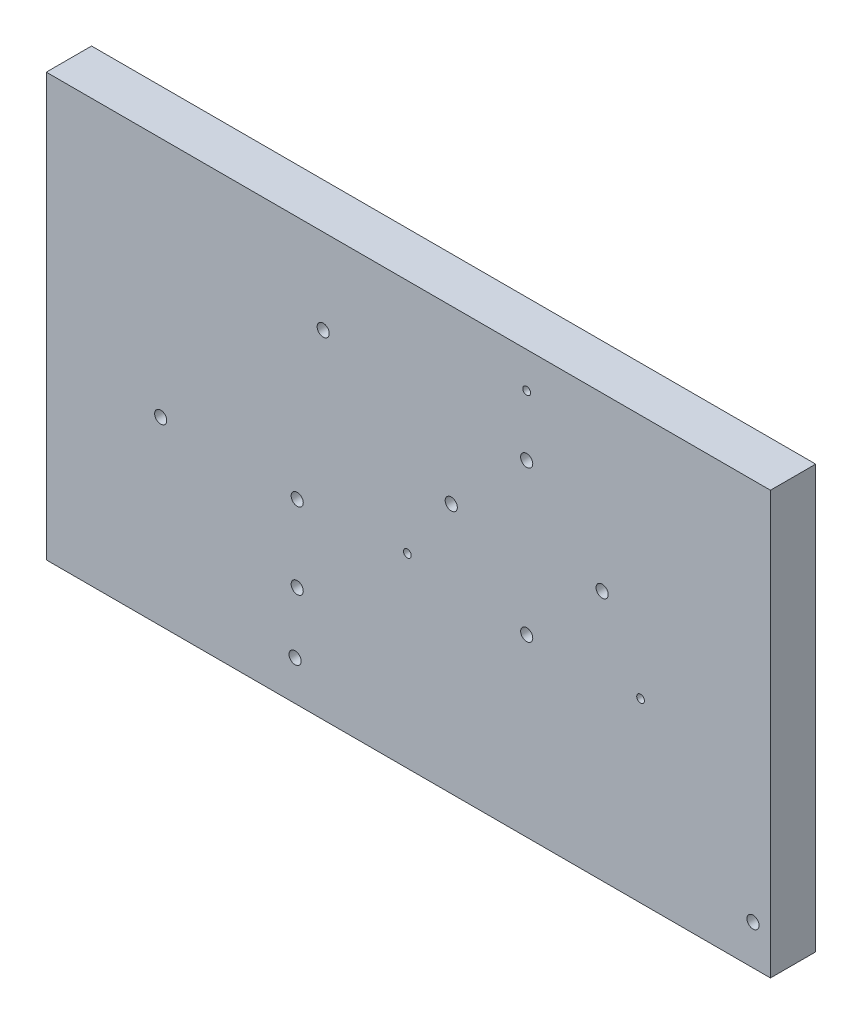
SolidWorks part; units mm, degrees
ref_plane "Front Plane" through (0, 0, 0) normal (0, 0, 1) x (1, 0, 0)
ref_plane "Top Plane" through (0, 0, 0) normal (0, 1, 0) x (1, 0, 0)
ref_plane "Right Plane" through (0, 0, 0) normal (1, 0, 0) x (0, 0, -1)
sketch "Sketch1" plane through (0, 0, 0) normal (0, 0, 1) x (1, 0, 0)
  line L1 (-152.4, -88.9) -> (152.4, -88.9)
  line L2 (-152.4, -88.9) -> (-152.4, 88.9)
  line L3 (-152.4, 88.9) -> (152.4, 88.9)
  line L4 (152.4, -88.9) -> (152.4, 88.9)
  line L5 (-152.4, -88.9) -> (152.4, 88.9) construction
  line L6 (-152.4, 88.9) -> (152.4, -88.9) construction
  point P0 (0, 0)
  dimension "D1" = 304.8
  dimension "D2" = 177.8
extrude "Boss-Extrude1" add sketch "Sketch1" against normal blind 19.05
sketch "Sketch2" plane through (0, 0, 0) normal (0, 0, 1) x (1, 0, 0)
  circle A1 centre (-104.2487, -12.7585) radius 2.5527
  circle A2 centre (-104.2487, -12.7585) radius 2.5527
  circle A3 centre (-46.7932, -46.1745) radius 2.5527
  circle A4 centre (-46.7932, -46.1745) radius 2.5527
  circle A5 centre (18.0555, 16.7132) radius 2.5527
  circle A6 centre (18.0555, 16.7132) radius 2.5527
  circle A7 centre (-35.8518, 53.1355) radius 2.5527
  circle A8 centre (-35.8518, 53.1355) radius 2.5527
  circle A9 centre (-47.6939, -72.1868) radius 2.5527
  circle A10 centre (-47.6939, -72.1868) radius 2.5527
  circle A11 centre (49.8055, 48.4632) radius 2.5527
  circle A12 centre (49.8055, 48.4632) radius 2.5527
  circle A13 centre (81.5555, 16.7132) radius 2.5527
  circle A14 centre (81.5555, 16.7132) radius 2.5527
  circle A15 centre (49.8055, -15.0368) radius 2.5527
  circle A16 centre (49.8055, -15.0368) radius 2.5527
  circle A17 centre (-46.7932, -14.0022) radius 2.5527
  circle A18 centre (-46.7932, -14.0022) radius 2.5527
  circle A19 centre (49.8055, 73.8632) radius 1.6319
  circle A20 centre (49.8055, 73.8632) radius 1.6319
  circle A21 centre (145.0555, -72.1868) radius 2.5527
  circle A22 centre (145.0555, -72.1868) radius 2.5527
  circle A23 centre (-0.4188, -10.5564) radius 1.6319
  circle A24 centre (-0.4188, -10.5564) radius 1.6319
  circle A25 centre (97.7356, -14.4129) radius 1.6319
  circle A26 centre (97.7356, -14.4129) radius 1.6319
  dimension "D1" = 0
  dimension "D2" = 0
  dimension "D3" = 0
  dimension "D4" = 0
  dimension "D5" = 0
  dimension "D6" = 0
  dimension "D7" = 0
  dimension "D8" = 0
  dimension "D9" = 0
  dimension "D10" = 0
  dimension "D11" = 0
  dimension "D12" = 0
  dimension "D13" = 0
extrude "Cut-Extrude1" cut sketch "Sketch2" against normal through all
